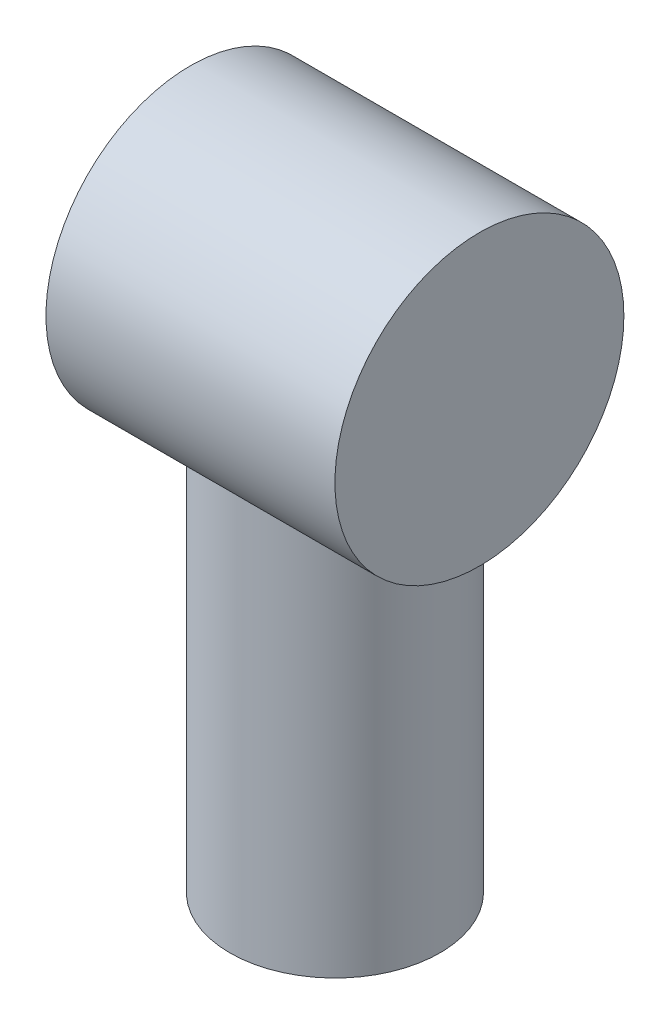
SolidWorks part; units mm, degrees
ref_plane "Front Plane" through (0, 0, 0) normal (0, 0, 1) x (1, 0, 0)
ref_plane "Top Plane" through (0, 0, 0) normal (0, 1, 0) x (1, 0, 0)
ref_plane "Right Plane" through (0, 0, 0) normal (1, 0, 0) x (0, 0, -1)
sketch "Sketch2" plane through (0, 0, 0) normal (0, 1, 0) x (1, 0, 0)
  circle A0 centre (0, 0) radius 40
  dimension "D1" = 80
extrude "Boss-Extrude2" add sketch "Sketch2" against normal blind 190
sketch "Sketch3" plane through (0, 0, 0) normal (1, 0, 0) x (0, 0, -1)
  circle A0 centre (0, 0) radius 55
  dimension "D1" = 110
extrude "Boss-Extrude3" add sketch "Sketch3" along normal mid plane 110
ref_axis "Axis1" through (0, -190, 0) along (0, 1, 0)
ref_axis "Axis2" through (0, -190, 0) along (0, 1, 0)
ref_axis "Axis3" through (0, -190, 0) along (0, 1, 0)
ref_axis "Axis4" through (55, 0, 0) along (-1, 0, 0)
ref_point "Point1"
